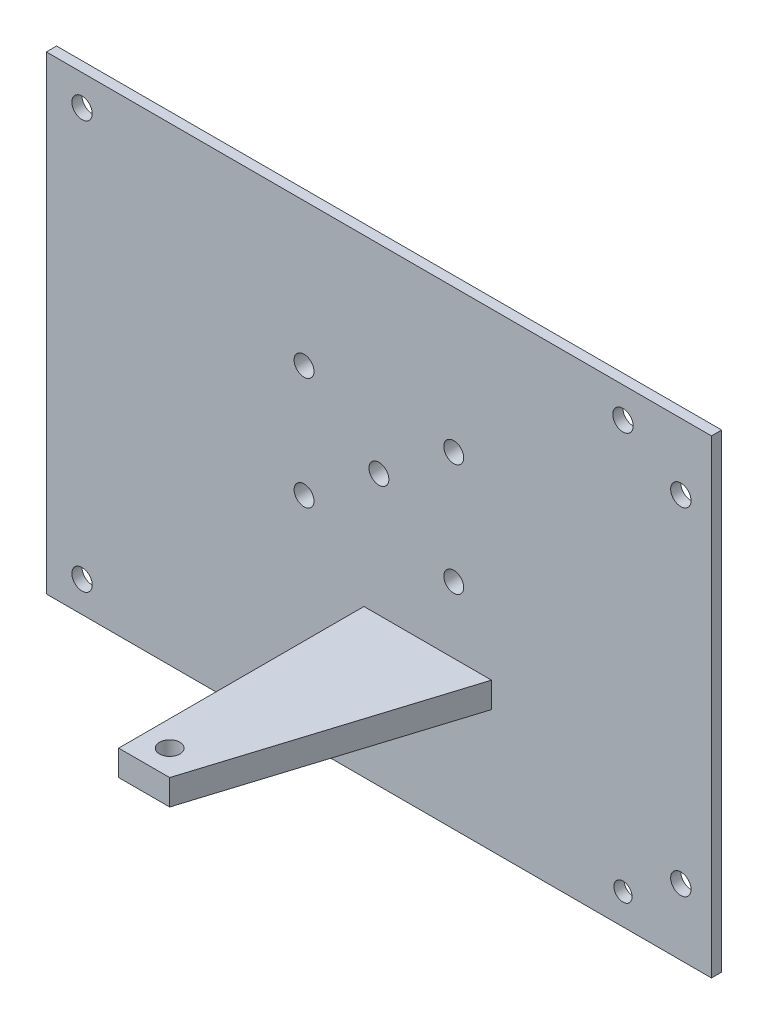
SolidWorks part; units mm, degrees
ref_plane "前视基准面" through (0, 0, 0) normal (0, 0, 1) x (1, 0, 0)
ref_plane "上视基准面" through (0, 0, 0) normal (0, 1, 0) x (1, 0, 0)
ref_plane "右视基准面" through (0, 0, 0) normal (1, 0, 0) x (0, 0, -1)
sketch "草图1" plane through (0, 0, 0) normal (0, 0, 1) x (1, 0, 0)
  line L0 (65.1699, 50) -> (97.0151, 50) construction
  line L3 (0, -3) -> (130.3399, -3)
  line L4 (0, -3) -> (0, 89)
  line L5 (0, 89) -> (130.3399, 89)
  line L6 (130.3399, -3) -> (130.3399, 89)
  circle A1 centre (124.3399, 10) radius 2
  circle A2 centre (124.3399, 76) radius 2
  circle A3 centre (7, 3) radius 2
  circle A4 centre (113, 3) radius 1.7856
  circle A5 centre (7, 83) radius 2
  circle A6 centre (113, 83) radius 2
  circle A7 centre (65.1699, 50) radius 1.95
  dimension "D1" = 13
  dimension "D2" = 6
  dimension "D3" = 13
extrude "凸台-拉伸1" add sketch "草图1" along normal mid plane 2
sketch "草图2" plane through (0, -3, 0) normal (0, -1, 0) x (1, 0, 0)
  line L1 (0, 1) -> (130.3399, 1) construction
  line L4 (62.24, 49.07) -> (72.24, 49.07)
  line L5 (72.24, 49.07) -> (87.24, 1)
  line L6 (62.24, 49.07) -> (62.24, 1)
  line L8 (62.24, 1) -> (87.24, 1)
  circle A1 centre (67.24, 44.07) radius 2
extrude "凸台-拉伸2" add sketch "草图2" against normal blind 5 from offset 24 offset against normal yes
sketch "草图3" plane through (0, 0, -1) normal (0, 0, -1) x (-1, 0, 0)
  line L1 (-85.1699, 65) -> (-45.1699, 65)
  line L2 (-85.1699, 65) -> (-85.1699, 35)
  line L3 (-85.1699, 35) -> (-45.1699, 35)
  line L4 (-45.1699, 65) -> (-45.1699, 35)
  line L5 (-85.1699, 65) -> (-45.1699, 35) construction
  line L6 (-85.1699, 35) -> (-45.1699, 65) construction
  circle A0 centre (-79.8366, 61) radius 1.95
  circle A1 centre (-50.5033, 61) radius 1.95
  circle A2 centre (-50.5033, 39) radius 1.95
  circle A3 centre (-79.8366, 39) radius 1.95
  circle A4 centre (-65.1699, 50) radius 1.95
  point P0 (-65.1699, 50)
  dimension "D2" = 4
  dimension "D1" = 40
  dimension "D3" = 4
  dimension "D4" = 4
  dimension "D5" = 4
extrude "凸台-拉伸3" add sketch "草图3" along normal blind 6
sketch "草图5" plane through (0, 0, -1) normal (0, 0, -1) x (-1, 0, 0)
  circle A0 centre (-50.5033, 39) radius 1.95
  circle A1 centre (-79.8366, 39) radius 1.95
  circle A2 centre (-79.8366, 61) radius 1.95
  circle A3 centre (-50.5033, 61) radius 1.95
extrude "切除-拉伸3" cut sketch "草图5" along normal blind 6 from surface starting at face at (74.74, 23.5, 1)
